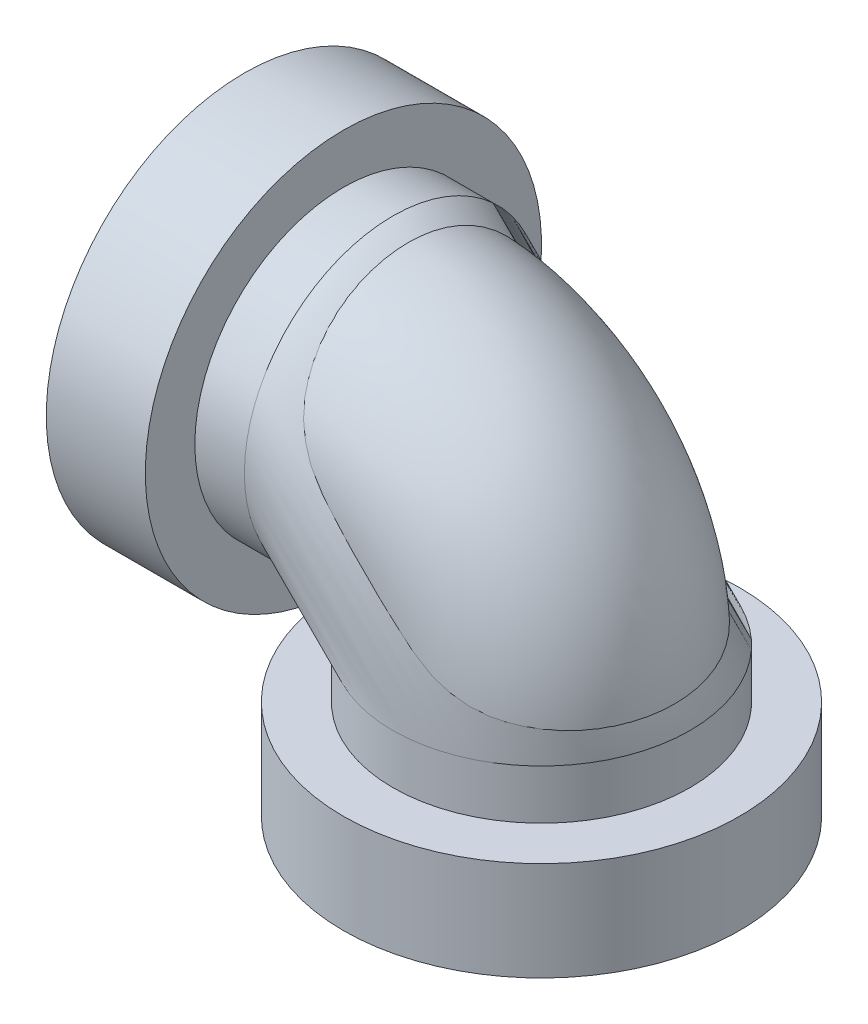
SolidWorks part; units mm, degrees
material "Malleable Cast Iron"
ref_plane "Front Plane" through (0, 0, 0) normal (0, 0, 1) x (1, 0, 0)
ref_plane "Top Plane" through (0, 0, 0) normal (0, 1, 0) x (1, 0, 0)
ref_plane "Right Plane" through (0, 0, 0) normal (1, 0, 0) x (0, 0, -1)
sketch "Sketch2" plane through (0, 0, 0) normal (0, 0, 1) x (1, 0, 0)
  line L0 (0, 0) -> (0, 15)
  line L1 (-15, 30) -> (-30, 30)
  arc A0 (-15, 30) -> (0, 15) centre (-15, 15) cw
  point P6 (0, 30)
  dimension "D3" = 15
  dimension "D1" = 30
  dimension "D2" = 30
sweep "Sweep1" add path "Sketch2" circular profile diameter 30 parameters "D3"=30
sketch "Sketch11" plane through (0, 0, 0) normal (0, 1, 0) x (1, 0, 0)
  circle A0 centre (0, 0) radius 13.5
  circle A1 centre (0, 0) radius 13.5
  circle A2 centre (0, 0) radius 15
  circle A3 centre (0, 0) radius 20
  dimension "D1" = 27
  dimension "D2" = 30
  dimension "D3" = 40
sweep "Cut-Sweep1" cut path "Sketch2<2>" circular profile diameter 27 parameters "D3"=27
sketch "Sketch2<2>" plane through (0, 0, 0) normal (0, 0, 1) x (1, 0, 0) same geometry as "Sketch2"
extrude "Boss-Extrude3" add sketch "Sketch11" along normal blind 10 separate body contours A3 A2 region at (-19.4343, 0, 0)
sketch "Sketch27" plane through (-30, 0, 0) normal (-1, 0, 0) x (0, 0, 1)
  circle A0 centre (0, 30) radius 15
  circle A1 centre (0, 30) radius 20
  dimension "D1" = 30
  dimension "D2" = 40
extrude "Boss-Extrude6" add sketch "Sketch27" against normal blind 10 separate body
